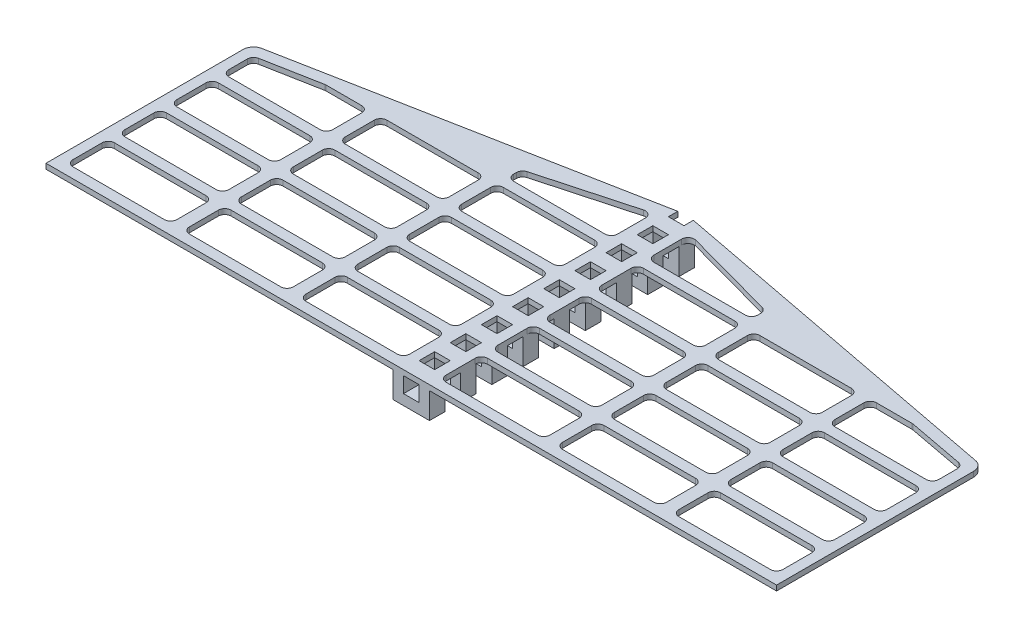
SolidWorks part; units mm, degrees
material "Balsa"
ref_plane "Front Plane" through (0, 0, 0) normal (0, 0, 1) x (1, 0, 0)
ref_plane "Top Plane" through (0, 0, 0) normal (0, 1, 0) x (1, 0, 0)
ref_plane "Right Plane" through (0, 0, 0) normal (1, 0, 0) x (0, 0, -1)
sketch "Sketch1" plane through (0, 0, 0) normal (0, 1, 0) x (1, 0, 0)
  line L0 (0, 0) -> (437.0222, 0)
  line L1 (426.7145, 253.437) -> (0, 335.28)
  line L2 (0, 335.28) -> (0, 0)
  line L3 (437.0222, 0) -> (437.0222, 240.9644)
  arc A0 (426.7145, 253.437) -> (437.0222, 240.9644) centre (424.3222, 240.9644) cw
  point P7 (437.0222, 251.46)
  dimension "D4" = 12.7
  dimension "D1" = 335.28
  dimension "D2" = 437.0222
  dimension "D3" = 251.46
extrude "Boss-Extrude1" add sketch "Sketch1" along normal blind 6.35
sketch "Sketch2" plane through (0, 6.35, 0) normal (0, 1, 0) x (1, 0, 0)
  line L0 (0, 0) -> (437.0222, 0) construction
  line L1 (20.32, 12.7) -> (132.08, 12.7)
  line L2 (12.7, 20.32) -> (12.7, 55.88)
  line L3 (20.32, 63.5) -> (132.08, 63.5)
  line L4 (139.7, 20.32) -> (139.7, 55.88)
  line L9 (0, 335.28) -> (0, 0) construction
  line L10 (155.045, 20.32) -> (155.045, 55.88)
  line L11 (162.665, 12.7) -> (274.425, 12.7)
  line L12 (282.045, 20.32) -> (282.045, 55.88)
  line L13 (162.665, 63.5) -> (274.425, 63.5)
  line L14 (297.3901, 20.32) -> (297.3901, 55.88)
  line L15 (305.0101, 12.7) -> (416.7701, 12.7)
  line L16 (424.3901, 20.32) -> (424.3901, 55.88)
  line L17 (305.0101, 63.5) -> (416.7701, 63.5)
  line L18 (155.045, 83.82) -> (155.045, 119.38)
  line L19 (162.665, 76.2) -> (274.425, 76.2)
  line L20 (282.045, 83.82) -> (282.045, 119.38)
  line L21 (162.665, 127) -> (274.425, 127)
  line L22 (297.3901, 83.82) -> (297.3901, 119.38)
  line L23 (305.0101, 76.2) -> (416.7701, 76.2)
  line L24 (424.3901, 83.82) -> (424.3901, 119.38)
  line L25 (305.0101, 127) -> (416.7701, 127)
  line L26 (155.045, 147.32) -> (155.045, 182.88)
  line L27 (162.665, 139.7) -> (274.425, 139.7)
  line L28 (282.045, 147.32) -> (282.045, 182.88)
  line L29 (162.665, 190.5) -> (274.425, 190.5)
  line L30 (297.3901, 147.32) -> (297.3901, 182.88)
  line L31 (305.0101, 139.7) -> (416.7701, 139.7)
  line L32 (424.3901, 147.32) -> (424.3901, 182.88)
  line L33 (305.0101, 190.5) -> (416.7701, 190.5)
  line L34 (155.045, 210.82) -> (155.045, 246.38)
  line L35 (162.665, 203.2) -> (274.425, 203.2)
  line L36 (282.045, 210.82) -> (282.045, 246.38)
  line L37 (162.665, 254) -> (274.425, 254)
  line L38 (297.3901, 210.82) -> (297.3901, 246.38)
  line L39 (305.0101, 203.2) -> (416.7701, 203.2)
  line L40 (424.3901, 210.82) -> (424.3901, 233.5456)
  line L41 (305.0101, 254) -> (348.5374, 254)
  line L50 (12.7, 83.82) -> (12.7, 119.38)
  line L51 (20.32, 76.2) -> (132.08, 76.2)
  line L52 (139.7, 83.82) -> (139.7, 119.38)
  line L53 (20.32, 127) -> (132.08, 127)
  line L54 (12.7, 147.32) -> (12.7, 182.88)
  line L55 (20.32, 139.7) -> (132.08, 139.7)
  line L56 (139.7, 147.32) -> (139.7, 182.88)
  line L57 (20.32, 190.5) -> (132.08, 190.5)
  line L58 (12.7, 210.8976) -> (12.7, 246.3024)
  line L59 (20.3976, 203.2) -> (132.0024, 203.2)
  line L60 (139.7, 210.8976) -> (139.7, 246.3024)
  line L61 (20.3976, 254) -> (132.0024, 254)
  line L62 (12.7, 274.3976) -> (12.7, 308.3078)
  line L63 (20.3976, 266.7) -> (132.0024, 266.7)
  line L64 (139.7, 274.3976) -> (139.7, 277.7658)
  line L66 (22.4294, 315.7324) -> (134.0343, 285.1904)
  line L68 (12.7, 317.5) -> (106.9847, 317.5) [skipped]
  line L69 (154.94, 317.5) -> (281.94, 317.5) [skipped]
  line L70 (282.045, 364.4738) -> (282.045, 415.2738) [skipped]
  line L71 (297.3901, 266.7) -> (297.3901, 317.5) [skipped]
  line L72 (297.18, 317.5) -> (424.18, 317.5) [skipped]
  line L73 (424.3901, 266.7) -> (424.3901, 317.5) [skipped]
  line L74 (297.18, 266.7) -> (424.18, 266.7) [skipped]
  line L75 (349.946, 253.8687) -> (418.1787, 241.0342)
  line L77 (162.665, 266.7) -> (200.4554, 266.7) [skipped]
  line L78 (155.045, 286.9363) -> (155.045, 297.2637) [skipped]
  arc A0 (20.32, 12.7) -> (12.7, 20.32) centre (20.32, 20.32) cw
  arc A1 (12.7, 55.88) -> (20.32, 63.5) centre (20.32, 55.88) cw
  arc A2 (132.08, 63.5) -> (139.7, 55.88) centre (132.08, 55.88) cw
  arc A3 (132.08, 12.7) -> (139.7, 20.32) centre (132.08, 20.32) ccw
  arc A4 (155.045, 20.32) -> (162.665, 12.7) centre (162.665, 20.32) ccw
  arc A5 (155.045, 55.88) -> (162.665, 63.5) centre (162.665, 55.88) cw
  arc A6 (282.045, 55.88) -> (274.425, 63.5) centre (274.425, 55.88) ccw
  arc A7 (274.425, 12.7) -> (282.045, 20.32) centre (274.425, 20.32) ccw
  arc A8 (416.7701, 12.7) -> (424.3901, 20.32) centre (416.7701, 20.32) ccw
  arc A9 (297.3901, 20.32) -> (305.0101, 12.7) centre (305.0101, 20.32) ccw
  arc A10 (297.3901, 55.88) -> (305.0101, 63.5) centre (305.0101, 55.88) cw
  arc A11 (424.3901, 55.88) -> (416.7701, 63.5) centre (416.7701, 55.88) ccw
  arc A12 (424.3901, 119.38) -> (416.7701, 127) centre (416.7701, 119.38) ccw
  arc A13 (416.7701, 76.2) -> (424.3901, 83.82) centre (416.7701, 83.82) ccw
  arc A14 (297.3901, 83.82) -> (305.0101, 76.2) centre (305.0101, 83.82) ccw
  arc A15 (297.3901, 119.38) -> (305.0101, 127) centre (305.0101, 119.38) cw
  arc A16 (282.045, 119.38) -> (274.425, 127) centre (274.425, 119.38) ccw
  arc A17 (282.045, 83.82) -> (274.425, 76.2) centre (274.425, 83.82) cw
  arc A18 (155.045, 83.82) -> (162.665, 76.2) centre (162.665, 83.82) ccw
  arc A19 (155.045, 119.38) -> (162.665, 127) centre (162.665, 119.38) cw
  arc A20 (139.7, 119.38) -> (132.08, 127) centre (132.08, 119.38) ccw
  arc A21 (132.08, 76.2) -> (139.7, 83.82) centre (132.08, 83.82) ccw
  arc A22 (12.7, 83.82) -> (20.32, 76.2) centre (20.32, 83.82) ccw
  arc A23 (12.7, 119.38) -> (20.32, 127) centre (20.32, 119.38) cw
  arc A24 (12.7, 147.32) -> (20.32, 139.7) centre (20.32, 147.32) ccw
  arc A25 (12.7, 182.88) -> (20.32, 190.5) centre (20.32, 182.88) cw
  arc A26 (139.7, 182.88) -> (132.08, 190.5) centre (132.08, 182.88) ccw
  arc A27 (132.08, 139.7) -> (139.7, 147.32) centre (132.08, 147.32) ccw
  arc A28 (155.045, 147.32) -> (162.665, 139.7) centre (162.665, 147.32) ccw
  arc A29 (155.045, 182.88) -> (162.665, 190.5) centre (162.665, 182.88) cw
  arc A30 (274.425, 139.7) -> (282.045, 147.32) centre (274.425, 147.32) ccw
  arc A31 (282.045, 182.88) -> (274.425, 190.5) centre (274.425, 182.88) ccw
  arc A32 (297.3901, 182.88) -> (305.0101, 190.5) centre (305.0101, 182.88) cw
  arc A33 (297.3901, 147.32) -> (305.0101, 139.7) centre (305.0101, 147.32) ccw
  arc A34 (416.7701, 139.7) -> (424.3901, 147.32) centre (416.7701, 147.32) ccw
  arc A35 (424.3901, 182.88) -> (416.7701, 190.5) centre (416.7701, 182.88) ccw
  arc A36 (418.1787, 241.0342) -> (424.3901, 233.5456) centre (416.7701, 233.5456) cw
  arc A37 (348.5374, 254) -> (349.946, 253.8687) centre (348.5374, 246.38) cw
  arc A38 (297.3901, 210.82) -> (305.0101, 203.2) centre (305.0101, 210.82) ccw
  arc A39 (416.7701, 203.2) -> (424.3901, 210.82) centre (416.7701, 210.82) ccw
  arc A40 (297.3901, 246.38) -> (305.0101, 254) centre (305.0101, 246.38) cw
  arc A41 (155.045, 246.38) -> (162.665, 254) centre (162.665, 246.38) cw
  arc A42 (155.045, 210.82) -> (162.665, 203.2) centre (162.665, 210.82) ccw
  arc A44 (274.425, 203.2) -> (282.045, 210.82) centre (274.425, 210.82) ccw
  arc A45 (282.045, 246.38) -> (274.425, 254) centre (274.425, 246.38) ccw
  arc A48 (139.7, 246.3024) -> (132.0024, 254) centre (132.0024, 246.3024) ccw
  arc A49 (132.0024, 203.2) -> (139.7, 210.8976) centre (132.0024, 210.8976) ccw
  arc A50 (12.7, 210.8976) -> (20.3976, 203.2) centre (20.3976, 210.8976) ccw
  arc A51 (12.7, 246.3024) -> (20.3976, 254) centre (20.3976, 246.3024) cw
  arc A52 (12.7, 274.3976) -> (20.3976, 266.7) centre (20.3976, 274.3976) ccw
  arc A53 (132.0024, 266.7) -> (139.7, 274.3976) centre (132.0024, 274.3976) ccw
  arc A54 (139.7, 277.7658) -> (134.0343, 285.1904) centre (132.0024, 277.7658) ccw
  arc A55 (12.7, 308.3078) -> (22.4294, 315.7324) centre (20.3976, 308.3078) cw
  point P46 (12.7, 12.7)
  point P49 (12.7, 63.5)
  point P82 (139.7, 63.5)
  dimension "D7" = 7.62
  dimension "D1" = 127
  dimension "D2" = 50.8
  dimension "D3" = 12.7
  dimension "D4" = 12.7
  dimension "D5" = 3
  dimension "D6" = 5
extrude "Cut-Extrude1" cut sketch "Sketch2" against normal up to surface (6.35 mm away) up to face at (260.6005, 0, -166.3071)
sketch "Sketch3" plane through (0, 6.35, 0) normal (0, 1, 0) x (1, 0, 0)
  line L2 (0, 19.05) -> (0, 38.1)
  line L3 (0, 0) -> (-19.05, 0)
  line L4 (0, 0) -> (0, 19.05)
  line L5 (0, 19.05) -> (-19.05, 19.05)
  line L6 (-19.05, 0) -> (-19.05, 19.05)
  line L7 (0, 19.05) -> (-19.05, 19.05)
  line L8 (-19.05, 19.05) -> (-19.05, 38.1)
  line L9 (0, 38.1) -> (-19.05, 38.1)
  line L10 (0, 38.1) -> (0, 57.15)
  line L11 (0, 38.1) -> (-19.05, 38.1)
  line L12 (-19.05, 38.1) -> (-19.05, 57.15)
  line L13 (0, 57.15) -> (-19.05, 57.15)
  line L14 (0, 57.15) -> (0, 76.2)
  line L15 (0, 57.15) -> (-19.05, 57.15)
  line L16 (-19.05, 57.15) -> (-19.05, 76.2)
  line L17 (0, 76.2) -> (-19.05, 76.2)
  line L18 (0, 76.2) -> (0, 95.25)
  line L19 (0, 76.2) -> (-19.05, 76.2)
  line L20 (-19.05, 76.2) -> (-19.05, 95.25)
  line L21 (0, 95.25) -> (-19.05, 95.25)
  line L22 (0, 95.25) -> (0, 114.3)
  line L23 (0, 95.25) -> (-19.05, 95.25)
  line L24 (-19.05, 95.25) -> (-19.05, 114.3)
  line L25 (0, 114.3) -> (-19.05, 114.3)
  line L26 (0, 114.3) -> (0, 133.35)
  line L27 (0, 114.3) -> (-19.05, 114.3)
  line L28 (-19.05, 114.3) -> (-19.05, 133.35)
  line L29 (0, 133.35) -> (-19.05, 133.35)
  line L30 (0, 133.35) -> (0, 152.4)
  line L31 (0, 133.35) -> (-19.05, 133.35)
  line L32 (-19.05, 133.35) -> (-19.05, 152.4)
  line L33 (0, 152.4) -> (-19.05, 152.4)
  line L34 (0, 152.4) -> (0, 171.45)
  line L35 (0, 152.4) -> (-19.05, 152.4)
  line L36 (-19.05, 152.4) -> (-19.05, 171.45)
  line L37 (0, 171.45) -> (-19.05, 171.45)
  line L38 (0, 171.45) -> (0, 190.5)
  line L39 (0, 171.45) -> (-19.05, 171.45)
  line L40 (-19.05, 171.45) -> (-19.05, 190.5)
  line L41 (0, 190.5) -> (-19.05, 190.5)
  line L42 (0, 190.5) -> (0, 209.55)
  line L43 (0, 190.5) -> (-19.05, 190.5)
  line L44 (-19.05, 190.5) -> (-19.05, 209.55)
  line L45 (0, 209.55) -> (-19.05, 209.55)
  line L46 (0, 209.55) -> (0, 228.6)
  line L47 (0, 209.55) -> (-19.05, 209.55)
  line L48 (-19.05, 209.55) -> (-19.05, 228.6)
  line L49 (0, 228.6) -> (-19.05, 228.6)
  line L50 (0, 228.6) -> (0, 247.65)
  line L51 (0, 228.6) -> (-19.05, 228.6)
  line L52 (-19.05, 228.6) -> (-19.05, 247.65)
  line L53 (0, 247.65) -> (-19.05, 247.65)
  line L54 (0, 247.65) -> (0, 266.7)
  line L55 (0, 247.65) -> (-19.05, 247.65)
  line L56 (-19.05, 247.65) -> (-19.05, 266.7)
  line L57 (0, 266.7) -> (-19.05, 266.7)
  line L58 (0, 266.7) -> (0, 285.75)
  line L59 (0, 266.7) -> (-19.05, 266.7)
  line L60 (-19.05, 266.7) -> (-19.05, 285.75)
  line L61 (0, 285.75) -> (-19.05, 285.75)
  line L62 (0, 285.75) -> (0, 304.8)
  line L63 (0, 285.75) -> (-19.05, 285.75)
  line L64 (-19.05, 285.75) -> (-19.05, 304.8)
  line L65 (0, 304.8) -> (-19.05, 304.8)
  line L66 (0, 304.8) -> (0, 323.85)
  line L67 (0, 304.8) -> (-19.05, 304.8)
  line L68 (-19.05, 304.8) -> (-19.05, 323.85)
  line L69 (0, 323.85) -> (-19.05, 323.85)
  line L70 (0, 323.85) -> (0, 342.9)
  line L71 (0, 323.85) -> (-19.05, 323.85)
  line L72 (-19.05, 323.85) -> (-19.05, 342.9)
  line L73 (0, 342.9) -> (-19.05, 342.9)
  dimension "D2" = 19.05
  dimension "D3" = 19.05
  dimension "D4" = 18
extrude "Boss-Extrude2" add sketch "Sketch3" against normal up to surface (6.35 mm away) contours L6 L3 L4 L5 | L10 L13 L12 L9 | L18 L21 L20 L17 | L26 L29 L28 L25 | L34 L37 L36 L33 | L42 L45 L44 L41 | L50 L53 L52 L49 | L58 L61 L60 L57 | L66 L69 L68 L65 region at (-9.525, 6.35, -9.525) region at (-9.525, 6.35, -47.625) region at (-9.525, 6.35, -85.725) region at (-9.525, 6.35, -123.825) region at (-9.525, 6.35, -161.925) region at (-9.525, 6.35, -200.025) region at (-9.525, 6.35, -238.125) region at (-9.525, 6.35, -276.225) region at (-9.525, 6.35, -314.325) up to face at (76.6352, 0, -283.6709)
ref_plane "Plane1" through (-9.525, 0, 0) normal (-1, 0, 0) x (0, 0, 1)
mirror "Mirror1" about plane through (-9.525, 0, 0) normal (-1, 0, 0) of "Boss-Extrude1"
mirror "Mirror2" about plane through (-9.525, 0, 0) normal (-1, 0, 0) of "Cut-Extrude1"
sketch "Sketch5" plane through (0, 0, 0) normal (0, 0, 1) x (1, 0, 0)
  line L0 (-456.0722, 0) -> (437.0222, 0) construction
  line L1 (0, 0) -> (-19.05, 0)
  line L2 (0, 0) -> (0, -19.05)
  line L3 (0, -19.05) -> (-19.05, -19.05)
  line L4 (-19.05, 0) -> (-19.05, -19.05)
  line L6 (-31.75, 0) -> (12.7, 0)
  line L7 (-31.75, 0) -> (-31.75, -31.75)
  line L8 (-31.75, -31.75) -> (12.7, -31.75)
  line L9 (-19.05, 0) -> (0, 0)
  line L10 (0, 0) -> (0, 6.35)
  line L11 (0, 6.35) -> (-19.05, 6.35)
  line L12 (-19.05, 6.35) -> (-19.05, 0)
  line L13 (-19.05, 0) -> (0, 0)
  line L14 (0, 0) -> (0, 6.35)
  line L15 (0, 6.35) -> (-19.05, 6.35)
  line L16 (-19.05, 6.35) -> (-19.05, 0)
  line L17 (12.7, 0) -> (12.7, -31.75)
  line M5 (-456.0722, 0) -> (437.0222, 0)
  dimension "D1" = 19.05
  dimension "D2" = 19.05
  dimension "D3" = 0
  dimension "D4" = 0
  dimension "D5" = 12.7
  dimension "D6" = 31.75
  dimension "D7" = 12.7
extrude "Boss-Extrude3" add sketch "Sketch5" against normal blind 19.05 contours L17 L2 L3 L4 L7 L8 M5 region at (6.35, -0.5462, 0)
pattern_linear "LPattern1" count 9 spacing 38.1 along (0, 0, -1) of "Boss-Extrude3"
